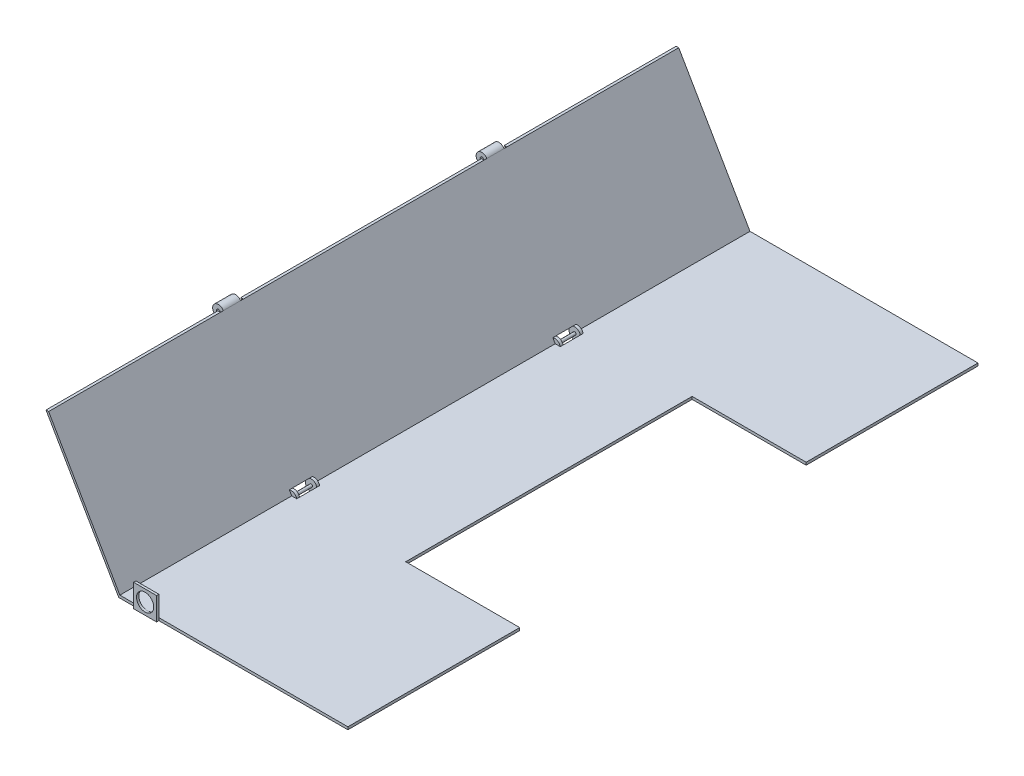
SolidWorks part; units mm, degrees
ref_plane "Front Plane" through (0, 0, 0) normal (0, 0, 1) x (1, 0, 0)
ref_plane "Top Plane" through (0, 0, 0) normal (0, 1, 0) x (1, 0, 0)
ref_plane "Right Plane" through (0, 0, 0) normal (1, 0, 0) x (0, 0, -1)
sketch "Sketch1" plane through (0, 0, 0) normal (0, 0, 1) x (1, 0, 0)
  line L0 (0, 0) -> (-63.5085, 110)
  line L1 (0, 0) -> (200, 0)
  line L2 (-63.5085, 110) -> (-61.2225, 110)
  line L3 (-61.2225, 110) -> (0.9662, 2.286)
  line L4 (0.9662, 2.286) -> (200, 2.286)
  line L5 (200, 2.286) -> (200, 0)
  dimension "D1" = 120
  dimension "D2" = 110
  dimension "D3" = 200
  dimension "D4" = 2.286
extrude "Boss-Extrude1" add sketch "Sketch1" along normal blind 550
sketch "Sketch2" plane through (0, 2.286, 0) normal (0, 1, 0) x (1, 0, 0)
  line L0 (200, -550) -> (200, 0) construction
  line L1 (200, -150) -> (100.4831, -150)
  line L2 (200, -150) -> (200, -400)
  line L3 (200, -400) -> (100.4831, -400)
  line L4 (100.4831, -150) -> (100.4831, -400)
  line L5 (200, 0) -> (0.9662, 0) construction
  point P6 (200, -275)
  point P7 (100.4831, 0)
  dimension "D1" = 250
extrude "Cut-Extrude1" cut sketch "Sketch2" against normal through all
sketch "Sketch4" plane through (0, 0, 150) normal (0, 0, 1) x (1, 0, 0)
  line L0 (0, 0) -> (200, 0) construction
  line L1 (0, 0) -> (200, 0)
  line L2 (200, 2.286) -> (0.9662, 2.286) construction
  line L3 (200, 2.286) -> (0.9662, 2.286)
  line L4 (0, 0) -> (0.9662, 2.286)
  circle A0 centre (0.4831, 1.143) radius 5
  circle A1 centre (0.4831, 1.143) radius 1.2409
  dimension "D1" = 10
extrude "Cut-Extrude2" cut sketch "Sketch4" along normal blind 20 contours A0
extrude "Boss-Extrude3" add sketch "Sketch4<3>" along normal blind 2.5 contours A0
sketch "Sketch4<3>" plane through (0, 0, 150) normal (0, 0, 1) x (1, 0, 0) same geometry as "Sketch4"
extrude "Boss-Extrude4" add sketch "Sketch4<5>" against normal blind 2.5 from offset 20 contours A0
sketch "Sketch4<5>" plane through (0, 0, 150) normal (0, 0, 1) x (1, 0, 0) same geometry as "Sketch4"
extrude "Boss-Extrude5" add sketch "Sketch4<7>" along normal blind 17.5 contours A1
sketch "Sketch4<7>" plane through (0, 0, 150) normal (0, 0, 1) x (1, 0, 0) same geometry as "Sketch4"
ref_plane "Plane2" through (0, 0, 275) normal (0, 0, 1) x (1, 0, 0)
mirror "Mirror1" about plane through (0, 0, 275) normal (0, 0, 1) of "Boss-Extrude5", "Boss-Extrude4", "Boss-Extrude3", "Cut-Extrude2"
sketch "Sketch5" plane through (0, 0, 550) normal (0, 0, 1) x (1, 0, 0)
  line L0 (0.9662, 2.286) -> (-61.2225, 110) construction
  line L1 (0.9662, 2.286) -> (-61.2225, 110)
  circle A0 centre (-65.5527, 107.5) radius 5
  circle A1 centre (-65.5527, 107.5) radius 1.5
  point P5 (-61.2225, 110)
  dimension "D1" = 10
  dimension "D2" = 3
extrude "Boss-Extrude6" add sketch "Sketch5" against normal blind 19.5 from offset 150 contours A0 | A1 offset against normal yes
extrude "Cut-Extrude5" cut sketch "Sketch5<4>" against normal blind 2.5 from offset 167.5 contours A0 offset against normal yes
sketch "Sketch5<4>" plane through (0, 0, 550) normal (0, 0, 1) x (1, 0, 0) same geometry as "Sketch5"
extrude "Cut-Extrude6" cut sketch "Sketch5<6>" against normal blind 2.5 from offset 150 contours A0 offset against normal yes
sketch "Sketch5<6>" plane through (0, 0, 550) normal (0, 0, 1) x (1, 0, 0) same geometry as "Sketch5"
mirror "Mirror2" about plane through (0, 0, 275) normal (0, 0, 1) of "Cut-Extrude6", "Cut-Extrude5", "Boss-Extrude6"
sketch "Sketch7" plane through (0, 0, 550) normal (0, 0, 1) x (1, 0, 0)
  line L0 (0, 0) -> (200, 0) construction
  line L1 (15, 0) -> (35, 0)
  line L2 (15, 0) -> (15, 20)
  line L3 (15, 20) -> (35, 20)
  line L4 (35, 0) -> (35, 20)
  line L5 (15, 20) -> (35, 0)
  circle A0 centre (25, 10) radius 7.5
  line M1 (0, 0) -> (200, 0)
  line M3 (200, 2.286) -> (0.9662, 2.286)
  dimension "D4" = 15
  dimension "D1" = 15
  dimension "D2" = 20
  dimension "D3" = 20
extrude "Boss-Extrude7" add sketch "Sketch7" along normal blind 2 contours A0 L5 L4 L3 M3 | A0 L5 L2 M3 | L5 L2 M3 M1 | L5 L4 M3 region at (24.44, 1.1199, 550) region at (34.238, 1.524, 550) region at (15.2505, 11.143, 550) region at (33.857, 2.5532, 550)
